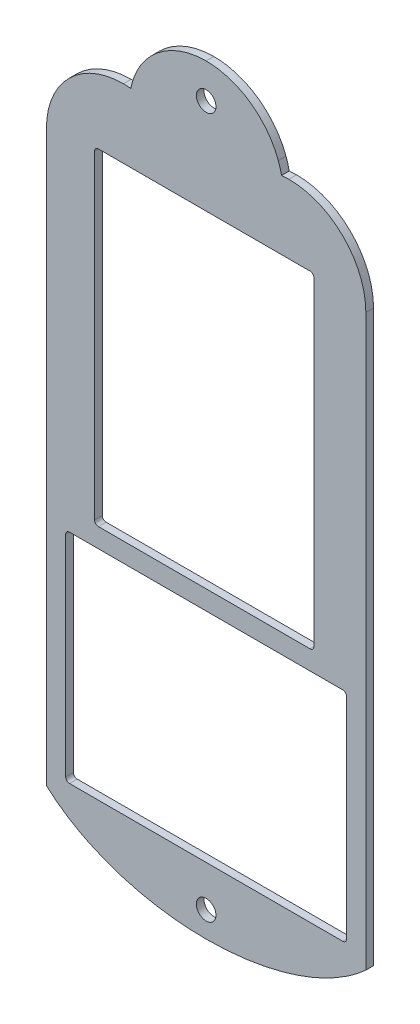
SolidWorks part; units mm, degrees
ref_plane "前视基准面" through (0, 0, 0) normal (0, 0, 1) x (1, 0, 0)
ref_plane "上视基准面" through (0, 0, 0) normal (0, 1, 0) x (1, 0, 0)
ref_plane "右视基准面" through (0, 0, 0) normal (1, 0, 0) x (0, 0, -1)
other "Configuration Table"
sketch "草图1" plane through (0, 0, 0) normal (0, 0, 1) x (1, 0, 0)
  line L0 (-84.75, 68.1509) -> (-84.75, -79.8491)
  line L1 (-1.7484, 68.1509) -> (-1.7484, -79.8491)
  line L3 (-71.25, 70.2249) -> (-16.2484, 70.2249)
  line L4 (-72.25, 69.2249) -> (-72.25, -13.7751)
  line L5 (-71.25, -14.7751) -> (-16.2484, -14.7751)
  line L6 (-15.2484, 69.2249) -> (-15.2484, -13.7751)
  line L10 (-78.75, -19.7751) -> (-7.7484, -19.7751)
  line L11 (-79.75, -20.7751) -> (-79.75, -75.3491)
  line L12 (-78.75, -76.3491) -> (-7.7484, -76.3491)
  line L13 (-6.7484, -20.7751) -> (-6.7484, -75.3491)
  circle A0 centre (-43.2492, 95.0101) radius 2.55
  circle A1 centre (-43.2492, -86.9899) radius 2.55
  arc A2 (-79.75, -75.3491) -> (-78.75, -76.3491) centre (-78.75, -75.3491) ccw
  arc A3 (-7.7484, -76.3491) -> (-6.7484, -75.3491) centre (-7.7484, -75.3491) ccw
  arc A4 (-7.7484, -19.7751) -> (-6.7484, -20.7751) centre (-7.7484, -20.7751) cw
  arc A5 (-72.25, -13.7751) -> (-71.25, -14.7751) centre (-71.25, -13.7751) ccw
  arc A6 (-78.75, -19.7751) -> (-79.75, -20.7751) centre (-78.75, -20.7751) ccw
  arc A7 (-16.2484, -14.7751) -> (-15.2484, -13.7751) centre (-16.2484, -13.7751) ccw
  arc A8 (-16.2484, 70.2249) -> (-15.2484, 69.2249) centre (-16.2484, 69.2249) cw
  arc A9 (-71.25, 70.2249) -> (-72.25, 69.2249) centre (-71.25, 69.2249) ccw
  spline S0 degree 3 poles (-1.7484, 68.1509) (-1.7484, 79.1964) (-10.7019, 88.1499) (-21.7474, 88.1499) knots 0 0 0 0 1 1 1 1
  spline S1 degree 3 poles (-21.7474, 88.1499) (-22.3894, 88.1499) (-23.028, 88.1181) (-23.6559, 88.0581) knots 1 1 1 1 2 2 2 2
  spline S2 degree 3 poles (-23.6559, 88.0581) (-23.8605, 89.0565) (-24.1427, 90.0302) (-24.4885, 90.9721) knots 2 2 2 2 3 3 3 3
  spline S3 degree 3 poles (-24.4885, 90.9721) (-27.3107, 98.5921) (-34.6449, 104.0249) (-43.2492, 104.0249) knots 3 3 3 3 4 4 4 4
  spline S4 degree 3 poles (-43.2492, 104.0249) (-51.8534, 104.0249) (-59.1877, 98.5921) (-62.0099, 90.9721) knots 4 4 4 4 5 5 5 5
  spline S5 degree 3 poles (-62.0099, 90.9721) (-62.3556, 90.0302) (-62.6379, 89.0565) (-62.8425, 88.0581) knots 5 5 5 5 6 6 6 6
  spline S6 degree 3 poles (-62.8425, 88.0581) (-63.4704, 88.1181) (-64.1054, 88.1499) (-64.7475, 88.1499) knots 6 6 6 6 7 7 7 7
  spline S7 degree 3 poles (-64.7475, 88.1499) (-75.7965, 88.1499) (-84.75, 79.1964) (-84.75, 68.1509) knots 7 7 7 7 8 8 8 8
  spline S8 degree 3 poles (-84.75, -79.8491) (-81.6385, -82.6925) (-77.8179, -85.1972) (-73.447, -87.268) knots 11 11 11 11 12 12 12 12
  spline S9 degree 3 poles (-73.447, -87.268) (-65.0297, -91.2579) (-54.5733, -93.618) (-43.2492, -93.618) knots 12 12 12 12 13 13 13 13
  spline S10 degree 3 poles (-43.2492, -93.618) (-31.925, -93.618) (-21.4687, -91.2579) (-13.0514, -87.268) knots 13 13 13 13 14 14 14 14
  spline S11 degree 3 poles (-13.0514, -87.268) (-8.6805, -85.1972) (-4.8599, -82.6925) (-1.7484, -79.8491) knots 14 14 14 14 15 15 15 15
  point P22 (0, 0)
  point P23 (0, 0)
  point P24 (0, 0)
  point P25 (0, 0)
  point P26 (0, 0)
  point P27 (0, 0)
  point P46 (-15.2484, 70.2249)
  point P49 (-72.25, 70.2249)
  dimension "D9" = 1
  dimension "D1" = 12.5
  dimension "D2" = 13.5
  dimension "D3" = 57.0016
  dimension "D4" = 33.8
  dimension "D5" = 5
  dimension "D6" = 5
  dimension "D7" = 5
  dimension "D8" = 3.5
extrude "凸台-拉伸1" add sketch "草图1" along normal blind 2
sketch "草图2" plane through (0, 0, 0) normal (0, 0, 1) x (1, 0, 0)
  line L0 (-84.75, 68.1509) -> (-84.75, -79.8491)
  line L1 (-1.7484, 68.1509) -> (-1.7484, -79.8491)
  line L3 (-73.2492, 69.5719) -> (-13.2492, 69.5719)
  line L4 (-73.2492, 69.5719) -> (-73.2492, -14.4281)
  line L5 (-73.2492, -14.4281) -> (-13.2492, -14.4281)
  line L6 (-13.2492, 69.5719) -> (-13.2492, -14.4281)
  line L10 (-79.2492, -19.4281) -> (-7.2492, -19.4281)
  line L11 (-79.2492, -19.4281) -> (-79.2492, -76.4281)
  line L12 (-79.2492, -76.4281) -> (-7.2492, -76.4281)
  line L13 (-7.2492, -19.4281) -> (-7.2492, -76.4281)
  circle A0 centre (-43.2492, 95.0101) radius 2.55
  circle A1 centre (-43.2492, -86.9899) radius 2.55
  spline S0 degree 3 poles (-1.7484, 68.1509) (-1.7484, 79.1964) (-10.7019, 88.1499) (-21.7474, 88.1499) knots 0 0 0 0 1 1 1 1
  spline S1 degree 3 poles (-21.7474, 88.1499) (-22.3894, 88.1499) (-23.028, 88.1181) (-23.6559, 88.0581) knots 1 1 1 1 2 2 2 2
  spline S2 degree 3 poles (-23.6559, 88.0581) (-23.8605, 89.0565) (-24.1427, 90.0302) (-24.4885, 90.9721) knots 2 2 2 2 3 3 3 3
  spline S3 degree 3 poles (-24.4885, 90.9721) (-27.3107, 98.5921) (-34.6449, 104.0249) (-43.2492, 104.0249) knots 3 3 3 3 4 4 4 4
  spline S4 degree 3 poles (-43.2492, 104.0249) (-51.8534, 104.0249) (-59.1877, 98.5921) (-62.0099, 90.9721) knots 4 4 4 4 5 5 5 5
  spline S5 degree 3 poles (-62.0099, 90.9721) (-62.3556, 90.0302) (-62.6379, 89.0565) (-62.8425, 88.0581) knots 5 5 5 5 6 6 6 6
  spline S6 degree 3 poles (-62.8425, 88.0581) (-63.4704, 88.1181) (-64.1054, 88.1499) (-64.7475, 88.1499) knots 6 6 6 6 7 7 7 7
  spline S7 degree 3 poles (-64.7475, 88.1499) (-75.7965, 88.1499) (-84.75, 79.1964) (-84.75, 68.1509) knots 7 7 7 7 8 8 8 8
  spline S8 degree 3 poles (-84.75, -79.8491) (-81.6385, -82.6925) (-77.8179, -85.1972) (-73.447, -87.268) knots 11 11 11 11 12 12 12 12
  spline S9 degree 3 poles (-73.447, -87.268) (-65.0297, -91.2579) (-54.5733, -93.618) (-43.2492, -93.618) knots 12 12 12 12 13 13 13 13
  spline S10 degree 3 poles (-43.2492, -93.618) (-31.925, -93.618) (-21.4687, -91.2579) (-13.0514, -87.268) knots 13 13 13 13 14 14 14 14
  spline S11 degree 3 poles (-13.0514, -87.268) (-8.6805, -85.1972) (-4.8599, -82.6925) (-1.7484, -79.8491) knots 14 14 14 14 15 15 15 15
  dimension "D4" = 5
